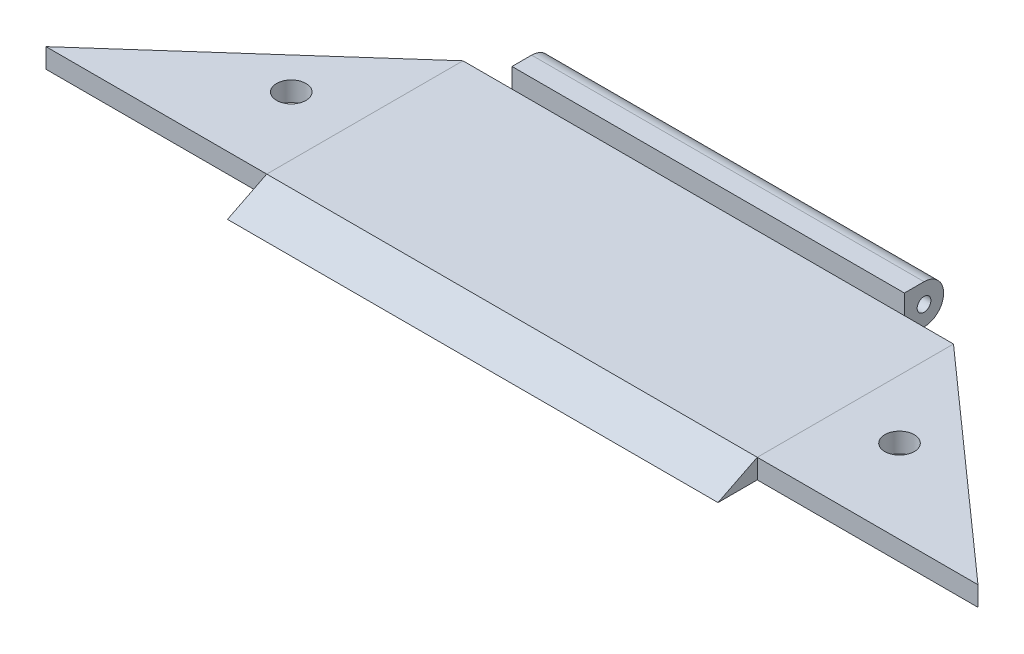
SolidWorks part; units mm, degrees
ref_plane "前视基准面" through (0, 0, 0) normal (0, 0, 1) x (1, 0, 0)
ref_plane "上视基准面" through (0, 0, 0) normal (0, 1, 0) x (1, 0, 0)
ref_plane "右视基准面" through (0, 0, 0) normal (1, 0, 0) x (0, 0, -1)
sketch "草图1" plane through (0, 0, 0) normal (1, 0, 0) x (0, 0, -1)
  line L0 (-87.0655, 0) -> (152.9345, 0)
  line L1 (152.9345, 0) -> (152.9345, 20)
  line L2 (152.9345, 20) -> (-47.0655, 20)
  line L3 (-47.0655, 20) -> (-87.0655, 0)
  line L4 (-87.0655, 0) -> (-87.8499, 0.5883)
  line L6 (152.9345, 0) -> (192.9345, 0)
  line L7 (152.9345, 0) -> (152.9345, 40)
  line L8 (152.9345, 40) -> (192.9345, 40)
  line L9 (192.9345, 0) -> (192.9345, 40)
  circle A0 centre (172.9345, 20) radius 7
  dimension "D1" = 200
  dimension "D2" = 240
  dimension "D3" = 20
  dimension "D4" = 40
  dimension "D5" = 40
extrude "凸台-拉伸1" add sketch "草图1" along normal blind 500 contours L6 L9 L8 L7 L1 A0 | L2 L3 L0 L1
sketch "草图2" plane through (0, 40, 0) normal (0, 1, 0) x (1, 0, 0)
  line L0 (500, 192.9345) -> (0, 192.9345) construction
  line L5 (500, 152.9345) -> (0, 152.9345) construction
  line L8 (0, 192.9345) -> (50, 192.9345)
  line L9 (0, 192.9345) -> (0, 152.9345)
  line L10 (0, 152.9345) -> (50, 152.9345)
  line L11 (50, 192.9345) -> (50, 152.9345)
  line L12 (450, 192.9345) -> (500, 192.9345)
  line L13 (450, 192.9345) -> (450, 152.9345)
  line L14 (450, 152.9345) -> (500, 152.9345)
  line L15 (500, 192.9345) -> (500, 152.9345)
  dimension "D1" = 400
  dimension "D2" = 50
  dimension "D3" = 40
  dimension "D4" = 50
extrude "切除-拉伸1" cut sketch "草图2" against normal blind 500
sketch "草图3" plane through (0, 20, 0) normal (0, 1, 0) x (1, 0, 0)
  line L0 (500, -47.0655) -> (725, -47.0655)
  line L1 (500, 152.9345) -> (725, -47.0655)
  line L2 (500, 152.9345) -> (500, -47.0655) construction
  line L3 (250, -47.0655) -> (250, 37.9345) construction
  line L4 (500, -47.0655) -> (0, -47.0655) construction
  line L5 (0, 152.9345) -> (-225, -47.0655)
  line L6 (0, -47.0655) -> (-225, -47.0655)
  circle A0 centre (560, 37.9345) radius 15
  circle A1 centre (-60, 37.9345) radius 15
  dimension "D2" = 30
  dimension "D1" = 225
  dimension "D3" = 60
  dimension "D4" = 85
extrude "凸台-拉伸2" add sketch "草图3" against normal blind 20 separate body
fillet "圆角2" radius 20 2 edges at (250, 0, -192.9345) (250, 40, -192.9345)
